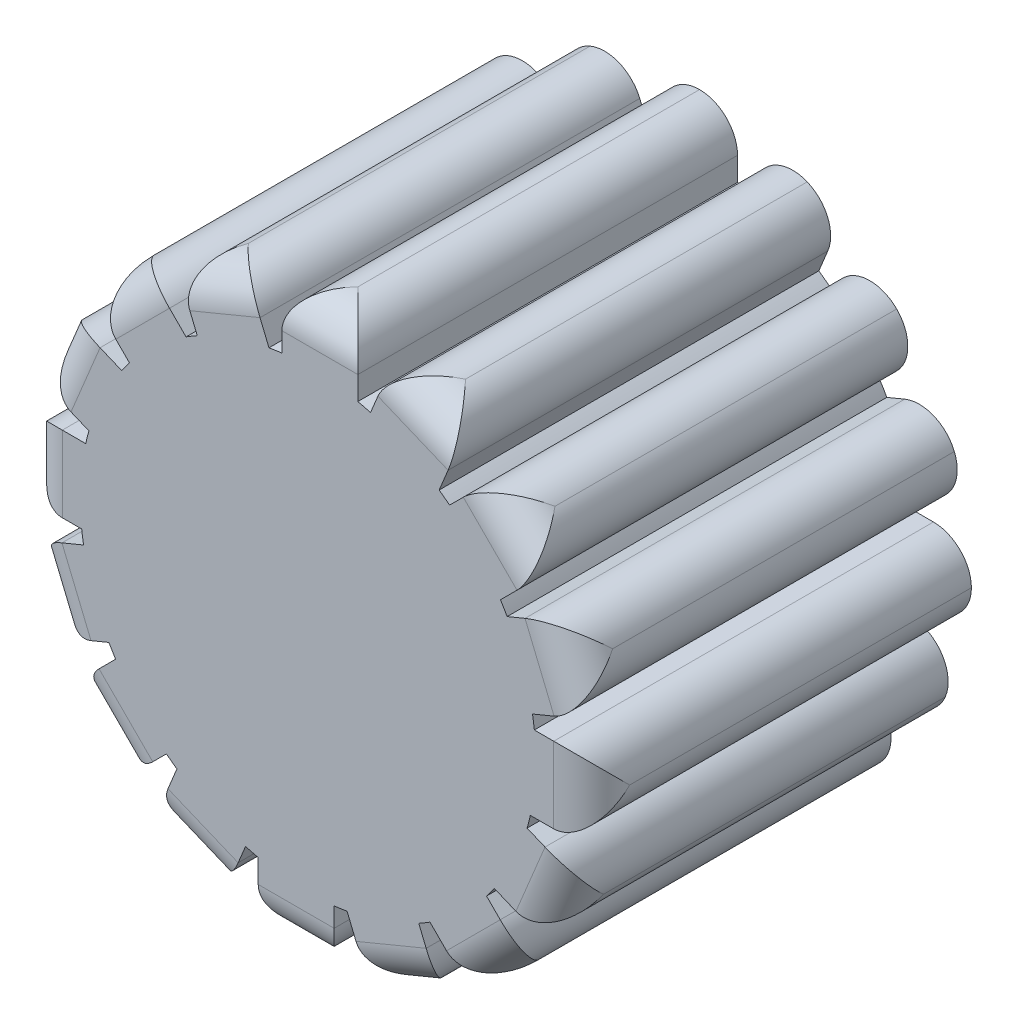
SolidWorks part; units mm, degrees
ref_plane "Front Plane" through (0, 0, 0) normal (0, 0, 1) x (1, 0, 0)
ref_plane "Top Plane" through (0, 0, 0) normal (0, 1, 0) x (1, 0, 0)
ref_plane "Right Plane" through (0, 0, 0) normal (1, 0, 0) x (0, 0, -1)
sketch "Sketch1" plane through (0, 0, 0) normal (0, 0, 1) x (1, 0, 0)
  circle A0 centre (-68.3905, -10.4636) radius 6
  point P3 (-68.3905, -10.4636)
  dimension "D1" = 12
extrude "Boss-Extrude3" add sketch "Sketch1" along normal blind 10
sketch "Sketch3" plane through (0, 0, 0) normal (0, 0, -1) x (-1, 0, 0)
  line L0 (71.0173, -12.0136) -> (65.7637, -12.0136)
  arc A0 (71.0173, -12.0136) -> (65.7637, -12.0136) centre (68.3905, -10.4636) ccw
  dimension "D1" = 6.1
  dimension "D2" = 4.6
extrude "Cut-Extrude1" cut sketch "Sketch3" against normal blind 8
sketch "Sketch4" plane through (0, 0, 0) normal (0, 0, -1) x (-1, 0, 0)
  circle A0 centre (68.3905, -10.4636) radius 4.5
  dimension "D1" = 9
extrude "Cut-Extrude2" cut sketch "Sketch4" against normal blind 3
sketch "Sketch6" plane through (0, 0, 10) normal (0, 0, 1) x (1, 0, 0)
  line L1 (-69.7027, -15.9349) -> (-67.7027, -15.9349)
  line L2 (-69.7027, -15.9349) -> (-69.7027, -17.9349)
  line L3 (-69.7027, -17.9349) -> (-67.7027, -17.9349)
  line L4 (-67.7027, -15.9349) -> (-67.7027, -17.9349)
  line L5 (-69.7027, -15.9349) -> (-67.7027, -17.9349) construction
  line L6 (-69.7027, -17.9349) -> (-67.7027, -15.9349) construction
  point P0 (-68.7027, -16.9349)
  dimension "D1" = 2
  dimension "D2" = 2
extrude "Boss-Extrude5" add sketch "Sketch6" against normal blind 10
fillet "Fillet8" radius 1 3 edges at (-68.7027, -17.9349, 10) (-67.7027, -17.9349, 5) (-69.7027, -17.9349, 5)
pattern_circular "CirPattern11" count 16 over 360 about axis through (-68.3905, -10.4636, 10) along (0, 0, -1) of "Boss-Extrude5", "Fillet8"
